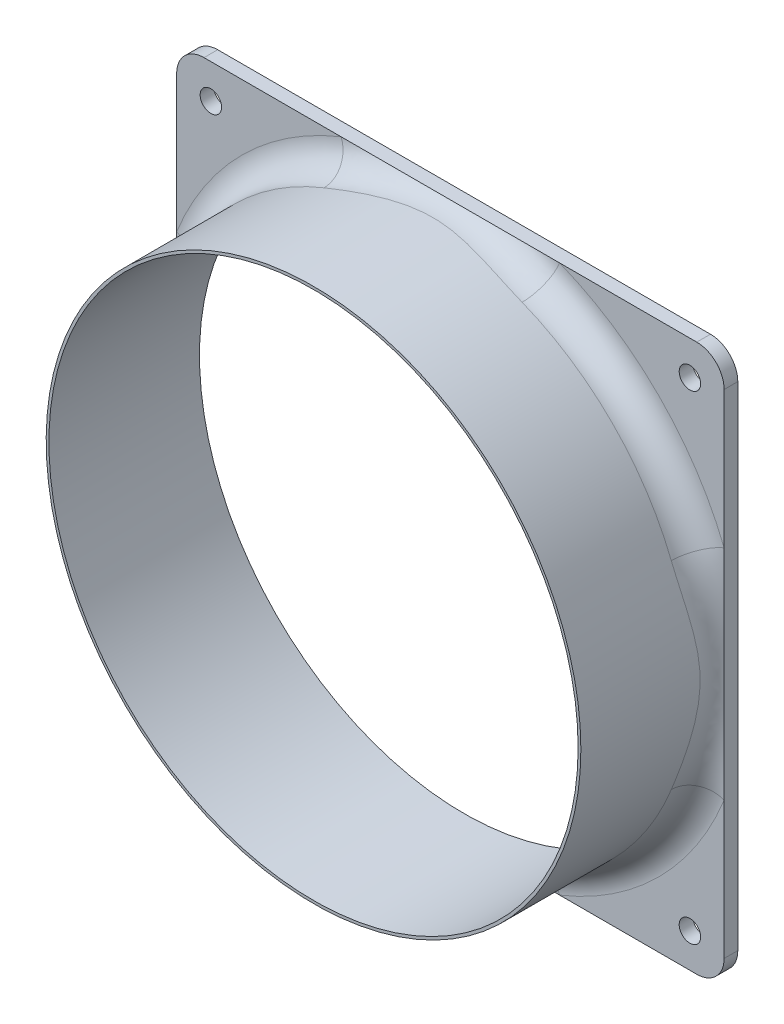
SolidWorks part; units mm, degrees
ref_plane "Front Plane" through (0, 0, 0) normal (0, 0, 1) x (1, 0, 0)
ref_plane "Top Plane" through (0, 0, 0) normal (0, 1, 0) x (1, 0, 0)
ref_plane "Right Plane" through (0, 0, 0) normal (1, 0, 0) x (0, 0, -1)
sketch "Sketch1" plane through (0, 0, 0) normal (0, 0, 1) x (1, 0, 0)
  line L0 (7.5, 112.5) -> (0, 120) construction
  line L1 (0, 0) -> (120, 0)
  line L2 (0, 0) -> (0, 120)
  line L3 (0, 120) -> (120, 120)
  line L4 (120, 0) -> (120, 120)
  line L5 (7.5, 112.5) -> (112.5, 112.5) construction
  line L6 (7.5, 112.5) -> (7.5, 7.5) construction
  line L7 (7.5, 7.5) -> (112.5, 7.5) construction
  line L8 (112.5, 112.5) -> (112.5, 7.5) construction
  line L9 (112.5, 112.5) -> (120, 120) construction
  line L10 (112.5, 7.5) -> (120, 0) construction
  line L11 (0, 60) -> (60, 60) construction
  line L12 (60, 60) -> (60, 120) construction
  circle A0 centre (7.5, 7.5) radius 2.35
  circle A1 centre (112.5, 7.5) radius 2.35
  circle A2 centre (112.5, 112.5) radius 2.35
  circle A3 centre (7.5, 112.5) radius 2.35
  circle A4 centre (60, 60) radius 58
  dimension "D2" = 4.7
  dimension "D4" = 116
  dimension "D1" = 120
  dimension "D3" = 105
extrude "Boss-Extrude1" add sketch "Sketch1" along normal blind 3
sketch "Sketch2" plane through (0, 0, 3) normal (0, 0, 1) x (1, 0, 0)
  circle A0 centre (60, 60) radius 58
  circle A1 centre (60, 60) radius 58.6
  dimension "D1" = 116
  dimension "D2" = 117.2
extrude "Boss-Extrude2" add sketch "Sketch2" along normal blind 30
fillet "Fillet1" radius 6 4 edges at (120, 0, 1.5) (120, 120, 1.5) (0, 0, 1.5) (0, 120, 1.5)
fillet "Fillet2" radius 6 1 edges at (1.4, 60, 3)
